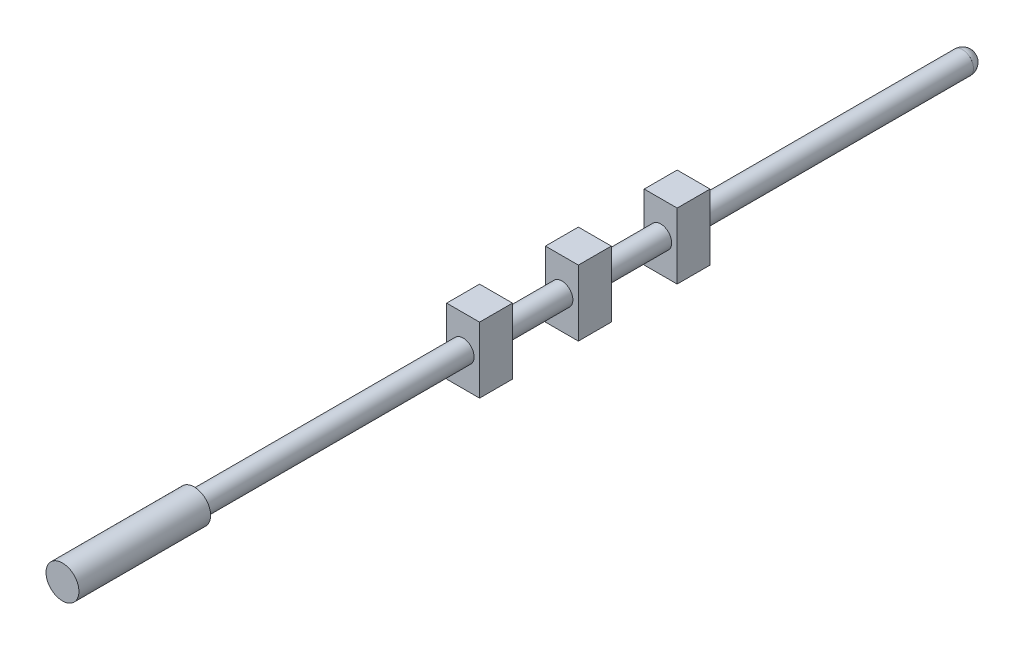
SolidWorks part; units mm, degrees
ref_plane "Front Plane" through (0, 0, 0) normal (0, 0, 1) x (1, 0, 0)
ref_plane "Top Plane" through (0, 0, 0) normal (0, 1, 0) x (1, 0, 0)
ref_plane "Right Plane" through (0, 0, 0) normal (1, 0, 0) x (0, 0, -1)
sketch "Sketch1" plane through (0, 0, 0) normal (0, 0, 1) x (1, 0, 0)
  circle A0 centre (0, 0) radius 25.4
  dimension "D1" = 50.8
extrude "Boss-Extrude1" add sketch "Sketch1" along normal blind 1778
sketch "Sketch2" plane through (0, 0, 1778) normal (0, 0, 1) x (1, 0, 0)
  circle A0 centre (0, 0) radius 38.1
extrude "Boss-Extrude2" add sketch "Sketch2" along normal blind 304.8
sketch "Sketch4" plane through (0, 0, 0) normal (0, 1, 0) x (1, 0, 0)
  line L0 (-25.4, 0) -> (-25.4, -1778) construction
  line L1 (-38.1, -850.9) -> (38.1, -850.9)
  line L2 (-38.1, -850.9) -> (-38.1, -927.1)
  line L3 (-38.1, -927.1) -> (38.1, -927.1)
  line L4 (38.1, -850.9) -> (38.1, -927.1)
  line L5 (38.1, -1778) -> (-38.1, -1778) construction
  line L6 (-38.1, -1079.5) -> (38.1, -1079.5)
  line L7 (-38.1, -1079.5) -> (-38.1, -1155.7)
  line L8 (-38.1, -1155.7) -> (38.1, -1155.7)
  line L9 (38.1, -1079.5) -> (38.1, -1155.7)
  line L10 (-38.1, -622.3) -> (38.1, -622.3)
  line L11 (-38.1, -622.3) -> (-38.1, -698.5)
  line L12 (-38.1, -698.5) -> (38.1, -698.5)
  line L13 (38.1, -622.3) -> (38.1, -698.5)
  point P16 (38.1, -889)
  dimension "D1" = 76.2
  dimension "D2" = 12.7
  dimension "D3" = 76.2
  dimension "D4" = 76.2
  dimension "D5" = 12.7
  dimension "D6" = 76.2
  dimension "D7" = 76.2
  dimension "D8" = 12.7
  dimension "D9" = 76.2
  dimension "D10" = 889
  dimension "D11" = 152.4
  dimension "D12" = 152.4
extrude "Boss-Extrude4" add sketch "Sketch4" along normal mid plane 152.4
sketch "Sketch5" plane through (0, 0, 0) normal (0, 0, -1) x (-1, 0, 0)
  circle A0 centre (0, 0) radius 25.4
extrude "Boss-Extrude5" add sketch "Sketch5" along normal blind 25.4 separate body
fillet "Fillet1" radius 25.4 1 edges at (-25.4, 0, -25.4)
